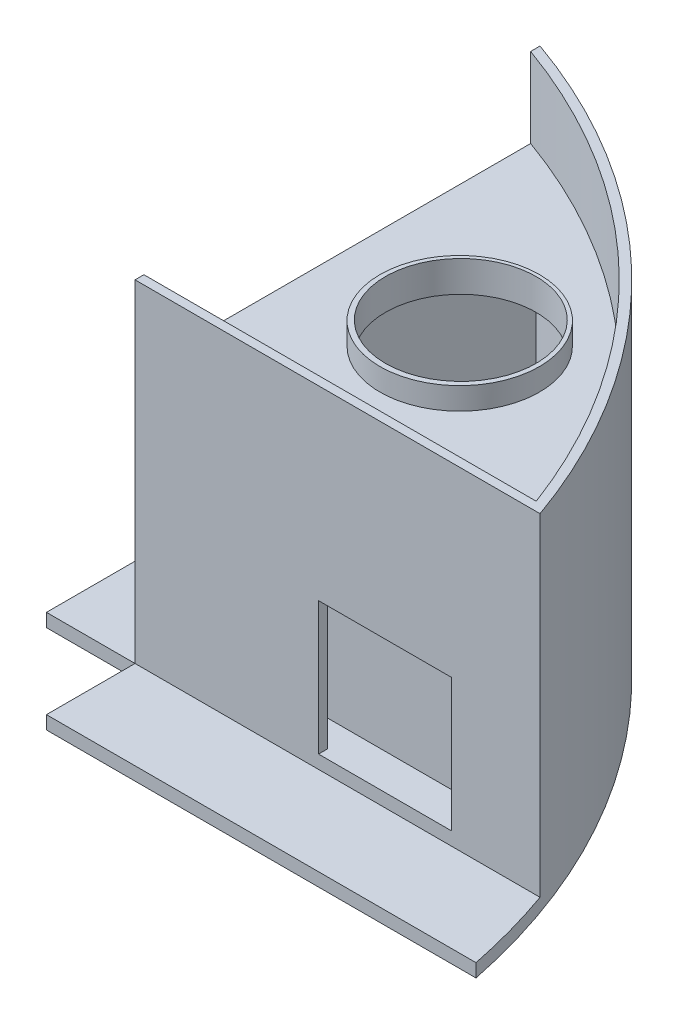
SolidWorks part; units mm, degrees
ref_plane "Front Plane" through (0, 0, 0) normal (0, 0, 1) x (1, 0, 0)
ref_plane "Top Plane" through (0, 0, 0) normal (0, 1, 0) x (1, 0, 0)
ref_plane "Right Plane" through (0, 0, 0) normal (1, 0, 0) x (0, 0, -1)
sketch "Sketch1" plane through (0, 0, 0) normal (0, 1, 0) x (1, 0, 0)
  line L9 (50, 30) -> (146.9694, 30)
  line L10 (146.9694, 30) -> (50, 30)
  line L11 (30, 50) -> (141.4214, 50)
  line L12 (141.4214, 50) -> (30, 50)
  line L13 (30, 50) -> (30, 146.9694)
  line L14 (30, 146.9694) -> (30, 50)
  line L15 (50, 30) -> (50, 141.4214)
  line L16 (50, 141.4214) -> (50, 30)
  arc A0 (146.9694, 30) -> (30, 146.9694) centre (0, 0) ccw
  dimension "D1" = 300
extrude "Boss-Extrude1" add sketch "Sketch1" along normal blind 3 contours L12 A0 L15 | L15 A0 L13 L11 | L9 A0 L12 L15 region at (97.2357, 0, -39.9022) region at (85.0087, 0, -85.0087) region at (39.9022, 0, -97.2357)
sketch "Sketch2" plane through (0, 3, 0) normal (0, 1, 0) x (-1, 0, 0)
  line L0 (-50, -50) -> (-141.4214, -50)
  line L1 (-141.4214, -50) -> (-50, -50)
  line L2 (-50, -50) -> (-50, -141.4214)
  line L3 (-50, -141.4214) -> (-50, -50)
  arc A0 (-146.9694, -30) -> (-30, -146.9694) centre (0, 0) ccw construction
  arc M4 (-146.9694, -30) -> (-30, -146.9694) centre (0, 0) ccw
extrude "Boss-Extrude2" add sketch "Sketch2" along normal blind 75 contours L2 L0 M4 region at (85.0087, 3, -85.0087)
shell "Shell2" thickness 2 removed face at (50, 49.875, -84.283)
sketch "Sketch3" plane through (0, 0, 0) normal (0, -1, 0) x (1, 0, 0)
  line L0 (50, -52) -> (50, -139.2982)
  line L1 (50, -139.2982) -> (50, -52)
  line L2 (138.5641, -52) -> (50, -52)
  arc A0 (50, -139.2982) -> (138.5641, -52) centre (0, 0) ccw
extrude "Boss-Extrude3" add sketch "Sketch3" against normal blind 6 contours L0 A0 L2 region at (83.7804, 0, -85.323)
sketch "Sketch4" plane through (0, 78, 0) normal (0, 1, 0) x (-1, 0, 0)
  line L0 (-50, -139.2982) -> (-50, -52)
  line L1 (-50, -52) -> (-138.5641, -52)
  arc A0 (-50, -139.2982) -> (-138.5641, -52) centre (0, 0) cw
extrude "Cut-Extrude1" cut sketch "Sketch4" against normal blind 2
sketch "Sketch5" plane through (0, 0, -50) normal (0, 0, 1) x (1, 0, 0)
  line L0 (91.4214, 36) -> (121.4214, 36)
  line L1 (121.4214, 36) -> (121.4214, 6)
  line L2 (121.4214, 6) -> (91.4214, 6)
  line L3 (91.4214, 6) -> (91.4214, 36)
  line L4 (50, 3) -> (141.4214, 3) construction
  line L5 (141.4214, 78) -> (141.4214, 3) construction
  dimension "D1" = 3
  dimension "D2" = 30
  dimension "D3" = 30
  dimension "D4" = 20
extrude "Cut-Extrude2" cut sketch "Sketch5" against normal blind 2 contours L3 L2 L1 L0 region at (106.4214, 21, -50)
sketch "Sketch6" plane through (0, 0, 0) normal (0, -1, 0) x (1, 0, 0)
  line L0 (136.1354, -58.0616) -> (50, -58.0616)
  line L1 (50, -50) -> (50, -141.4214) construction
  line L2 (50, -58.0616) -> (50, -139.2982)
  arc A0 (50, -139.2982) -> (138.5641, -52) centre (0, 0) ccw construction
  arc A1 (50, -139.2982) -> (136.1354, -58.0616) centre (0, 0) ccw
extrude "Boss-Extrude4" add sketch "Sketch6" against normal blind 60
sketch "Sketch7" plane through (0, 60, 0) normal (0, 1, 0) x (-1, 0, 0)
  line L0 (-50, -139.2982) -> (-50, -58.0616)
  line L1 (-50, -58.0616) -> (-136.1354, -58.0616)
  arc A0 (-50, -139.2982) -> (-136.1354, -58.0616) centre (0, 0) cw
shell "Shell3" thickness 2 removed face at (50, 52.35, -83.5852)
sketch "Sketch8" plane through (0, 60, 0) normal (0, 1, 0) x (1, 0, 0)
  circle A0 centre (81.609, 91.6854) radius 18
  dimension "D1" = 36
extrude "Boss-Extrude5" add sketch "Sketch8" along normal blind 5
sketch "Sketch9" plane through (0, 65, 0) normal (0, 1, 0) x (-1, 0, 0)
  circle A0 centre (-81.609, -91.9225) radius 17
  dimension "D1" = 34
extrude "Cut-Extrude3" cut sketch "Sketch9" against normal blind 7 contours A0 region at (81.609, 65, -91.9225)
sketch "Sketch10" plane through (0, 0, 0) normal (0, -1, 0) x (1, 0, 0)
  line L0 (50, -58.0616) -> (50, -139.2982)
  line L1 (52, -58.0616) -> (52, -138.5641)
  line L2 (50, -58.0616) -> (136.1354, -58.0616) construction
  line L3 (52, -58.0616) -> (50, -58.0616)
  arc A0 (50, -139.2982) -> (136.1354, -58.0616) centre (0, 0) ccw construction
  arc A1 (52, -138.5641) -> (50, -139.2982) centre (50.6329, -137.9312) cw
  dimension "D1" = 2
extrude "Boss-Extrude6" add sketch "Sketch10" against normal blind 60 contours L0 A1 L1 L3
